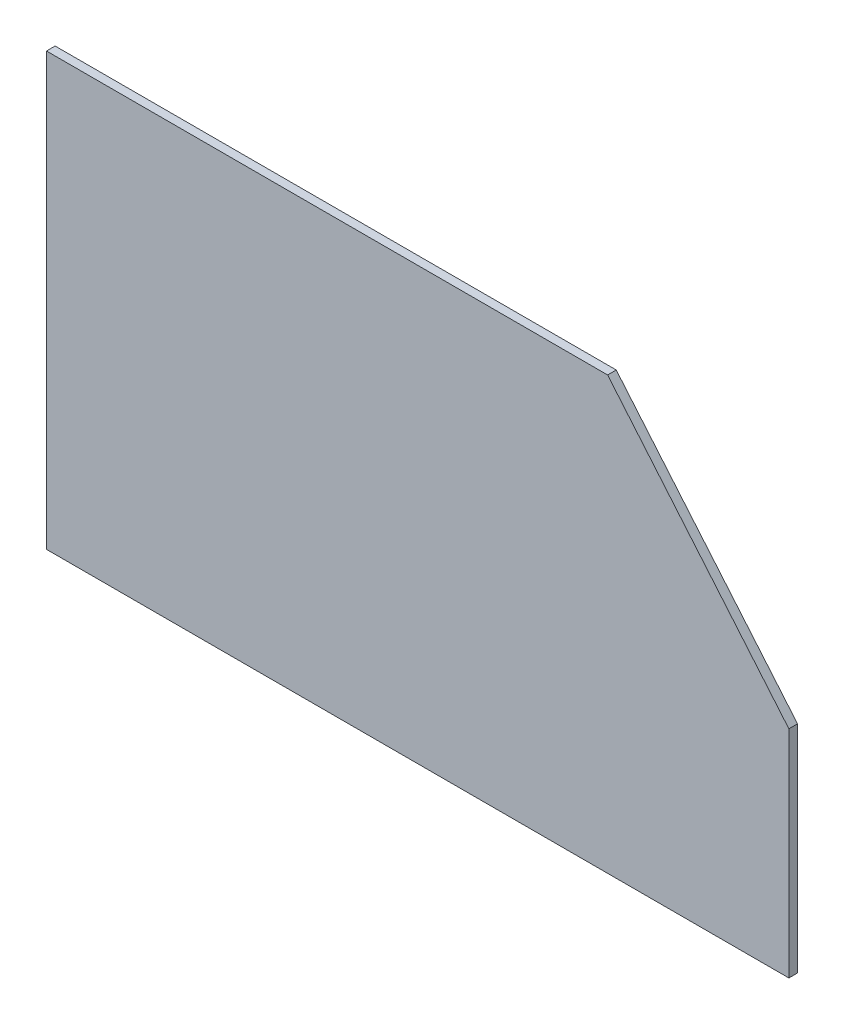
SolidWorks part; units mm, degrees
ref_plane "Front Plane" through (0, 0, 0) normal (0, 0, 1) x (1, 0, 0)
ref_plane "Top Plane" through (0, 0, 0) normal (0, 1, 0) x (1, 0, 0)
ref_plane "Right Plane" through (0, 0, 0) normal (1, 0, 0) x (0, 0, -1)
sketch "Sketch1" plane through (0, 0, 0) normal (0, 0, 1) x (1, 0, 0)
  line L0 (0, 0) -> (86, 0)
  line L1 (86, 0) -> (86, 25)
  line L2 (86, 25) -> (65, 50)
  line L3 (65, 50) -> (0, 50)
  line L4 (0, 50) -> (0, 0)
  dimension "D1" = 86
  dimension "D2" = 25
  dimension "D3" = 50
  dimension "D4" = 65
extrude "Boss-Extrude1" add sketch "Sketch1" along normal blind 1
